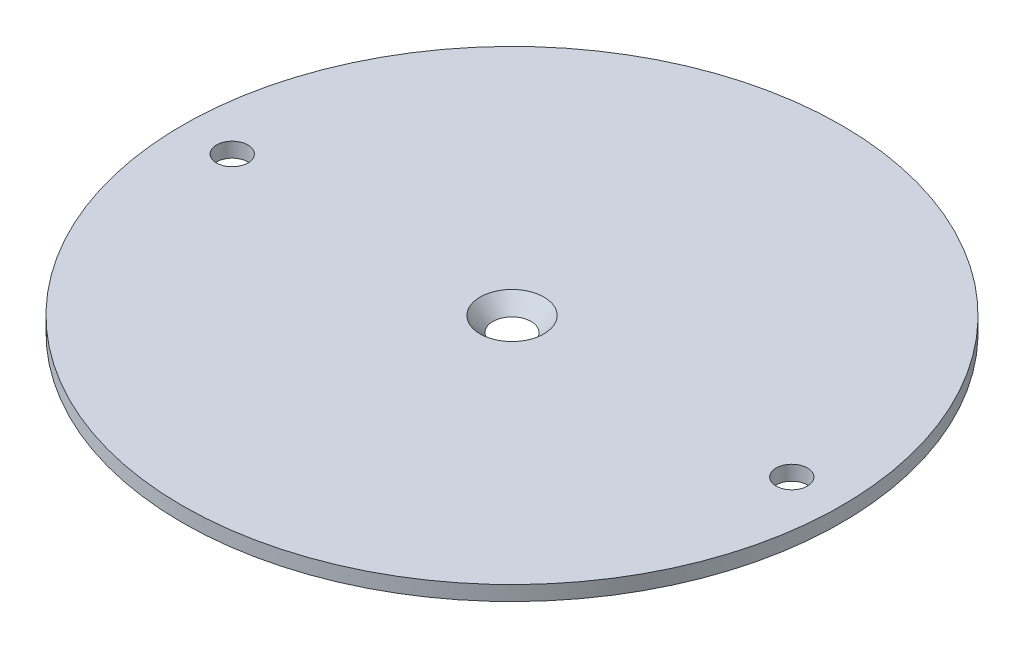
SolidWorks part; units mm, degrees
material "6061 Alloy"
ref_plane "Front Plane" through (0, 0, 0) normal (0, 0, 1) x (1, 0, 0)
ref_plane "Top Plane" through (0, 0, 0) normal (0, 1, 0) x (1, 0, 0)
ref_plane "Right Plane" through (0, 0, 0) normal (1, 0, 0) x (0, 0, -1)
sketch "Sketch2" plane through (0, 0, 0) normal (0, 1, 0) x (1, 0, 0)
  circle A0 centre (0, 0) radius 71.0565
  dimension "D1" = 142.113
extrude "Boss-Extrude1" add sketch "Sketch2" along normal blind 3.175
sketch "Sketch3" plane through (0, 3.175, 0) normal (0, 1, 0) x (1, 0, 0)
  point P0 (-60.325, 0)
  point P1 (60.325, 0)
  dimension "D1" = 60.325
  dimension "D2" = 60.325
hole_wizard "1/4 Clearance Hole1" positions "Sketch3" profile "Sketch4" hole size "1/4" standard "ANSI Inch" end condition through all
sketch "Sketch4" plane through (-60.325, 3.175, 0) normal (1, 0, 0) x (0, 0, 1)
  line L0 (0, 0) -> (0, 3.175)
  line L1 (0, 3.175) -> (3.3782, 3.175)
  line L2 (3.3782, 3.175) -> (3.3782, 0)
  line L5 (3.3782, 0) -> (0, 0)
  line L11 (0, -6.35) -> (0, 107.95) construction
  dimension "Thru Hole Dia." = 6.7564
  dimension "Thru Hole Depth" = 3.175
sketch "Sketch5" plane through (0, 3.175, 0) normal (0, 1, 0) x (1, 0, 0)
  point P0 (0, 0)
hole_wizard "CSK for 1/4 Flat Head Machine Screw1" positions "Sketch5" profile "Sketch7" countersink size "1/4" standard "ANSI Inch" end condition through all
sketch "Sketch7" plane through (0, 3.175, 0) normal (1, 0, 0) x (0, 0, 1)
  line L0 (0, 0) -> (0, 3.175)
  line L1 (0, 3.175) -> (3.3782, 3.175)
  line L2 (3.3782, 3.175) -> (3.3782, 4.0323)
  line L3 (3.3782, 4.0323) -> (6.8834, 0)
  line L5 (6.8834, 0) -> (0, 0)
  line L6 (-3.3782, 4.0323) -> (-6.8834, 0) construction
  line L11 (0, -6.35) -> (0, 107.95) construction
  dimension "Thru Hole Dia." = 6.7564
  dimension "Thru Hole Depth" = 3.175
  dimension "Near C'Sink Dia." = 13.7668
  dimension "Near C'Sink Angle" = 82
equation "\"outerdiameter\" = 5.595"
equation "\"platethickness\"= 1 / 8"
equation "\"holespacing\"= 2.375"
equation "\"D1@Sketch2\"=\"outerdiameter\""
equation "\"D1@Boss-Extrude1\"=\"platethickness\""
equation "\"D2@Sketch3\"=\"holespacing\""
equation "\"D1@Sketch3\"=\"holespacing\""
